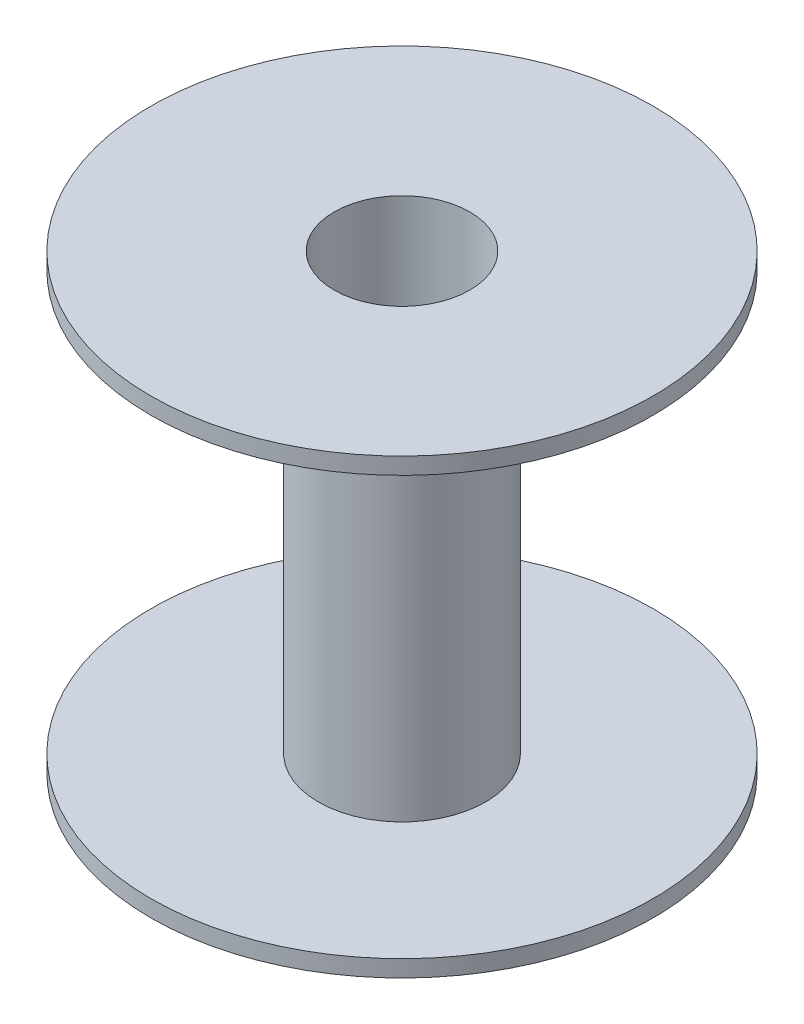
SolidWorks part; units mm, degrees
ref_plane "Front Plane" through (0, 0, 0) normal (0, 0, 1) x (1, 0, 0)
ref_plane "Top Plane" through (0, 0, 0) normal (0, 1, 0) x (1, 0, 0)
ref_plane "Right Plane" through (0, 0, 0) normal (1, 0, 0) x (0, 0, -1)
sketch "Sketch3" plane through (0, 0, 0) normal (0, 1, 0) x (1, 0, 0)
  circle A0 centre (0, 0) radius 5
  circle A1 centre (0, 0) radius 4.05
  dimension "D1" = 8.1
  dimension "D2" = 10
extrude "Boss-Extrude1" add sketch "Sketch3" along normal blind 25
sketch "Sketch20" plane through (0, 0, 0) normal (0, 0, 1) x (1, 0, 0)
  circle A0 centre (5, 0) radius 0.5
  dimension "D1" = 1
sketch "Sketch21" plane through (0, 25, 0) normal (0, 1, 0) x (1, 0, 0)
  circle A0 centre (0, 0) radius 15
  dimension "D1" = 30
extrude "Boss-Extrude2" add sketch "Sketch21" along normal blind 1
sketch "Sketch29" plane through (0, 26, 0) normal (0, 1, 0) x (1, 0, 0)
  circle A0 centre (0, 0) radius 1.75
  circle A1 centre (0, 0) radius 3
  dimension "D1" = 6
  dimension "D2" = 3.5
extrude "Cut-Extrude6" cut sketch "Sketch29" against normal blind 8.3 contours A0
sketch "Sketch33" plane through (0, 0, 0) normal (0, -1, 0) x (1, 0, 0)
  circle A0 centre (0, 0) radius 15
  dimension "D1" = 30
extrude "Boss-Extrude5" add sketch "Sketch33" along normal blind 1
sketch "Sketch35" plane through (0, -1, 0) normal (0, -1, 0) x (1, 0, 0)
  circle A0 centre (0, 0) radius 4.05
  dimension "D1" = 8.1
extrude "Cut-Extrude8" cut sketch "Sketch35" against normal up to surface (27 mm away) up to face at (0, 26, 1.75)
